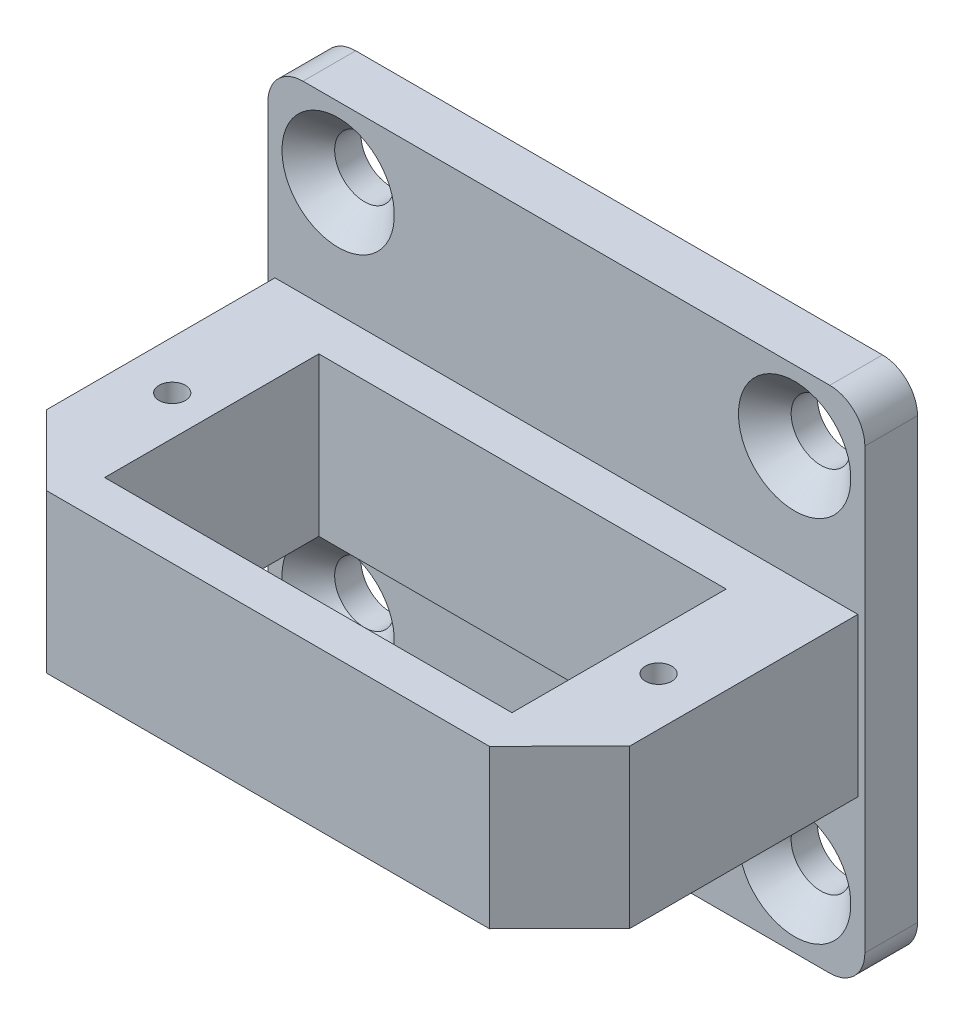
SolidWorks part; units mm, degrees
ref_plane "Front Plane" through (0, 0, 0) normal (0, 0, 1) x (1, 0, 0)
ref_plane "Top Plane" through (0, 0, 0) normal (0, 1, 0) x (1, 0, 0)
ref_plane "Right Plane" through (0, 0, 0) normal (1, 0, 0) x (0, 0, -1)
sketch "Sketch1" plane through (0, 0, 0) normal (0, 0, 1) x (1, 0, 0)
  line L1 (-17, -14.5) -> (17, -14.5)
  line L2 (-17, -14.5) -> (-17, 14.5)
  line L3 (-17, 14.5) -> (17, 14.5)
  line L4 (17, -14.5) -> (17, 14.5)
  line L5 (-17, -14.5) -> (17, 14.5) construction
  line L6 (-17, 14.5) -> (17, -14.5) construction
  circle A0 centre (-13, 10.5) radius 1.7
  circle A1 centre (13, 10.5) radius 1.7
  circle A2 centre (13, -10.5) radius 1.7
  circle A3 centre (-13, -10.5) radius 1.7
  point P12 (0, 0)
  dimension "D1" = 3.4
  dimension "D2" = 4
  dimension "D3" = 4
extrude "Boss-Extrude1" add sketch "Sketch1" along normal blind 3
ref_plane "Plane1" through (0, 0, 0) normal (0, -1, 0) x (-1, 0, 0)
sketch "Sketch3" plane through (0, 0, 0) normal (0, -1, 0) x (-1, 0, 0)
  line L0 (0, 0) -> (0, -3) construction
  line L1 (17, -3) -> (17, 0) construction
  line L2 (-11.6, -17.7) -> (11.6, -17.7)
  line L3 (-11.6, -17.7) -> (-11.6, -5.5)
  line L4 (-11.6, -5.5) -> (11.6, -5.5)
  line L5 (11.6, -17.7) -> (11.6, -5.5)
  line L6 (-11.6, -17.7) -> (11.6, -5.5) construction
  line L7 (-11.6, -5.5) -> (11.6, -17.7) construction
  line L8 (0, -3) -> (0, -11.6) construction
  line L9 (-13.85, -11.6) -> (13.85, -11.6) construction
  line L10 (16.6, -3) -> (16.6, -16)
  line L13 (-16.6, -3) -> (-16.6, -16)
  line L14 (16.6, -3) -> (-16.6, -3)
  line L15 (0, -11.6) -> (0, -20) construction
  line L16 (12.6128, -20) -> (-12.6128, -20)
  line L17 (16.6, -16) -> (12.6128, -20)
  line L18 (-12.6128, -20) -> (-16.6, -16)
  line L19 (17, -3) -> (-17, -3) construction
  circle A0 centre (-13.85, -11.6) radius 0.75
  circle A1 centre (13.85, -11.6) radius 0.75
  dimension "D4" = 1.5
  dimension "D1" = 23.2
  dimension "D2" = 12.2
  dimension "D3" = 27.7
  dimension "D5" = 5
  dimension "D6" = 2.5
  dimension "D7" = 2.3
  dimension "D8" = 13
extrude "Boss-Extrude2" add sketch "Sketch3" along normal blind 5 and the other way blind 4
fillet "Fillet1" radius 2 4 edges at (-17, 14.5, 1.5) (-17, -14.5, 1.5) (17, 14.5, 1.5) (17, -14.5, 1.5)
chamfer "Chamfer1" distance 1.5 angle 45 4 edges at (-11.3, 10.5, 3) (-11.3, -10.5, 3) (14.7, -10.5, 3) (14.7, 10.5, 3)
